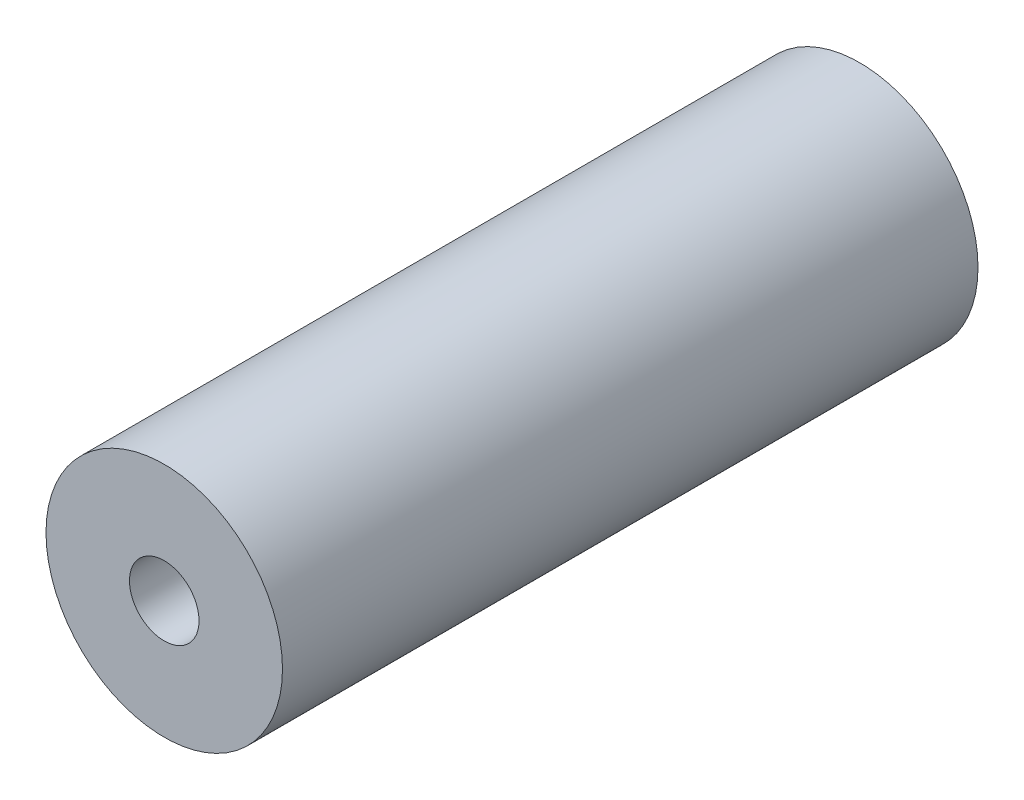
SolidWorks part; units mm, degrees
ref_plane "Front Plane" through (0, 0, 0) normal (0, 0, 1) x (1, 0, 0)
ref_plane "Top Plane" through (0, 0, 0) normal (0, 1, 0) x (1, 0, 0)
ref_plane "Right Plane" through (0, 0, 0) normal (1, 0, 0) x (0, 0, -1)
sketch "Sketch1" plane through (0, 0, 0) normal (0, 0, 1) x (1, 0, 0)
  circle A0 centre (0, 0) radius 2.5
  circle A1 centre (0, 0) radius 8.5
  dimension "D1" = 5
  dimension "D2" = 6
extrude "Boss-Extrude1" add sketch "Sketch1" along normal mid plane 50
